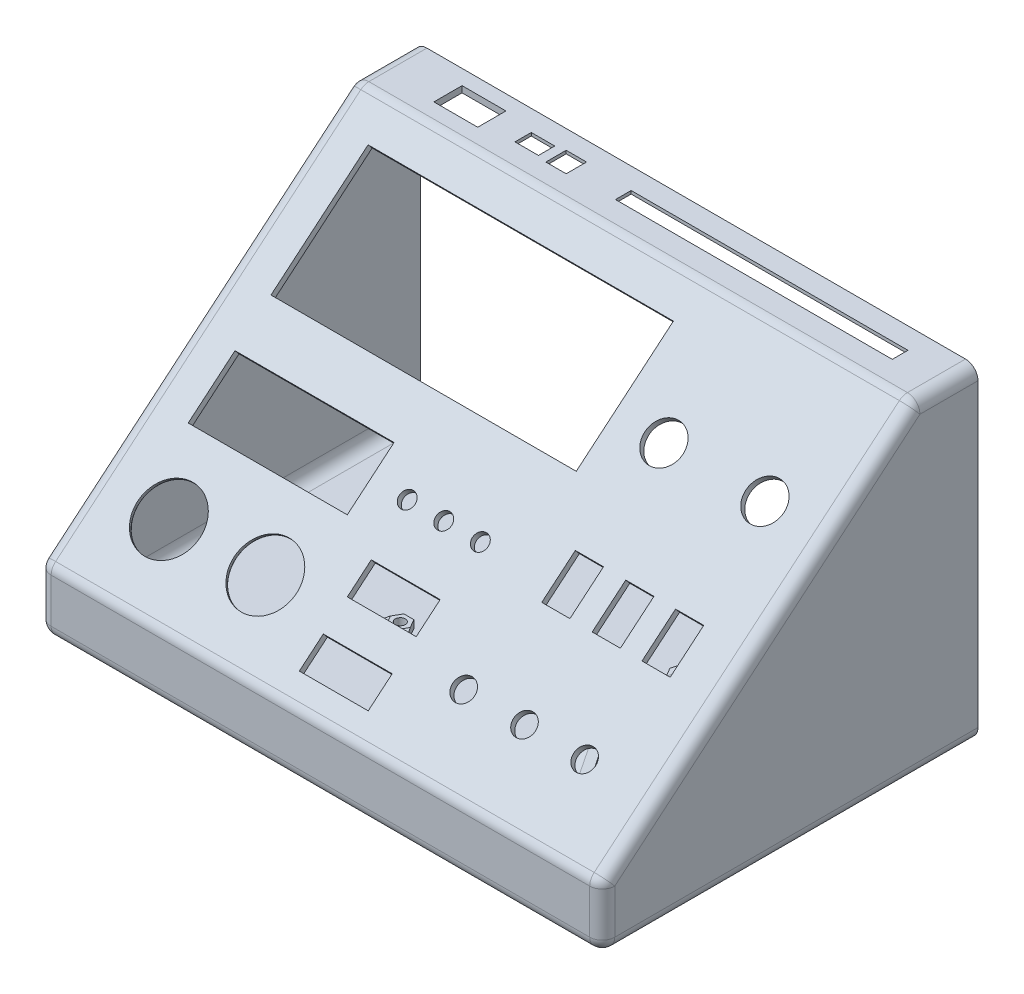
SolidWorks part; units mm, degrees
ref_plane "Front Plane" through (0, 0, 0) normal (0, 0, 1) x (1, 0, 0)
ref_plane "Top Plane" through (0, 0, 0) normal (0, 1, 0) x (1, 0, 0)
ref_plane "Right Plane" through (0, 0, 0) normal (1, 0, 0) x (0, 0, -1)
sketch "Sketch1" plane through (0, 0, 0) normal (0, 1, 0) x (1, 0, 0)
  line L1 (-90, -60) -> (90, -60)
  line L2 (-90, -60) -> (-90, 60)
  line L3 (-90, 60) -> (90, 60)
  line L4 (90, -60) -> (90, 60)
  line L5 (-90, -60) -> (90, 60) construction
  line L6 (-90, 60) -> (90, -60) construction
  point P0 (0, 0)
  dimension "D1" = 180
  dimension "D2" = 120
extrude "Boss-Extrude1" add sketch "Sketch1" along normal blind 20
sketch "Sketch2" plane through (-90, 0, 0) normal (-1, 0, 0) x (0, 0, 1)
  line L0 (60, 20) -> (-40, 103.91)
  line L1 (-60, 20) -> (60, 20) construction
  line L2 (60, 20) -> (60, 0) construction
  line L3 (-60, 20) -> (-60, 103.91)
  line L4 (-60, 103.91) -> (-40, 103.91)
  line L5 (-60, 20) -> (60, 20)
  dimension "D1" = 40
  dimension "D2" = 100
extrude "Boss-Extrude2" add sketch "Sketch2" against normal up to surface (180 mm away) up to face at (90, 10, 0)
shell "Shell3" thickness 2 removed face at (0, 51.955, -60)
fillet "Fillet1" radius 4 11 edges at (-90, 10, 60) (90, 10, 60) (0, 0, 60) (0, 20, 60) (-90, 61.955, 10) (0, 103.91, -40) (90, 61.955, 10) (-90, 103.91, -50) (-90, 0, 0) (90, 0, 0) (90, 103.91, -50)
fillet "Fillet2" radius 4 11 edges at (88, 10.5337, 58) (0, 19.0674, 58) (-88, 10.5337, 58) (0, 2, 58) (88, 101.91, -50.364) (0, 101.91, -40.7279) (-88, 101.91, -50.364) (88, 60.4887, 8.636) (88, 2, -1) (-88, 60.4887, 8.636) (-88, 2, -1)
sketch "Sketch4" plane through (0, 2, 0) normal (0, 1, 0) x (1, 0, 0)
  line L0 (-84, -54) -> (84, -54) construction
  line L1 (0, -54) -> (0, 60) construction
  line L2 (84, 60) -> (-84, 60) construction
  line L3 (0, 0) -> (0, 60) construction
  line L4 (0, 3) -> (0, 60) construction
  line L5 (0, 60) -> (0, 31.5) construction
  line L6 (0, 31.5) -> (0, 3) construction
  line L7 (0, 3) -> (0, 60.9981) construction
  line L8 (0, 60.9981) -> (0, 31.9991) construction
  line L9 (0, 31.9991) -> (0, 3) construction
  line L10 (0, -7.5005) -> (0, 42.4995)
  line L11 (35, 42.4995) -> (-35, 42.4995)
  line L12 (35, 42.4995) -> (35, -7.5005)
  line L13 (35, -7.5005) -> (-35, -7.5005)
  line L14 (-35, 42.4995) -> (-35, -7.5005)
  line L15 (35, 42.4995) -> (-35, -7.5005) construction
  line L16 (35, -7.5005) -> (-35, 42.4995) construction
  line L17 (35, -7.5005) -> (31, -7.5005)
  line L18 (31, -7.5005) -> (31, -3.5005)
  line L19 (34.1754, -3.5005) -> (32.5877, -0.7505)
  line L20 (32.5877, -0.7505) -> (29.4123, -0.7505)
  line L21 (29.4123, -0.7505) -> (27.8246, -3.5005)
  line L22 (27.8246, -3.5005) -> (29.4123, -6.2505)
  line L23 (29.4123, -6.2505) -> (32.5877, -6.2505)
  line L24 (32.5877, -6.2505) -> (34.1754, -3.5005)
  line L25 (-35, 17.4995) -> (35, 17.4995)
  line L26 (32.5877, 41.2495) -> (34.1754, 38.4995)
  line L27 (29.4123, 41.2495) -> (32.5877, 41.2495)
  line L28 (27.8246, 38.4995) -> (29.4123, 41.2495)
  line L29 (29.4123, 35.7495) -> (27.8246, 38.4995)
  line L30 (32.5877, 35.7495) -> (29.4123, 35.7495)
  line L31 (34.1754, 38.4995) -> (32.5877, 35.7495)
  line L32 (-29.4123, 41.2495) -> (-32.5877, 41.2495)
  line L33 (-27.8246, 38.4995) -> (-29.4123, 41.2495)
  line L34 (-29.4123, 35.7495) -> (-27.8246, 38.4995)
  line L35 (-32.5877, 35.7495) -> (-29.4123, 35.7495)
  line L36 (-34.1754, 38.4995) -> (-32.5877, 35.7495)
  line L37 (-32.5877, 41.2495) -> (-34.1754, 38.4995)
  line L38 (-32.5877, -6.2505) -> (-34.1754, -3.5005)
  line L39 (-29.4123, -6.2505) -> (-32.5877, -6.2505)
  line L40 (-27.8246, -3.5005) -> (-29.4123, -6.2505)
  line L41 (-29.4123, -0.7505) -> (-27.8246, -3.5005)
  line L42 (-32.5877, -0.7505) -> (-29.4123, -0.7505)
  line L43 (-34.1754, -3.5005) -> (-32.5877, -0.7505)
  circle A0 centre (31, -3.5005) radius 2.75 construction
  point P11 (0, 17.4995)
  dimension "D1" = 70
  dimension "D2" = 50
  dimension "D3" = 4
  dimension "D4" = 4
  dimension "D5" = 5.5
extrude "Boss-Extrude3" add sketch "Sketch4" along normal blind 2.5 contours L23 L24 L19 L20 L21 L22 | L31 L26 L27 L28 L29 L30 | L32 L37 L36 L35 L34 L33 | L43 L38 L39 L40 L41 L42 region at (30.2061, 2, 6.1665) region at (31, 2, -38.4995) region at (-31, 2, -38.4995) region at (-31, 2, 3.5005)
sketch "Sketch14" plane through (0, 4.5, 0) normal (0, 1, 0) x (1, 0, 0)
  line L0 (34.1754, -3.5005) -> (27.8246, -3.5005) construction
  line L1 (29.4123, -0.7505) -> (27.8246, -3.5005) construction
  line L2 (27.8246, -3.5005) -> (29.4123, -6.2505) construction
  line L3 (27.8246, -3.5005) -> (-27.8246, -3.5005) construction
  line L4 (-27.8246, -3.5005) -> (0, -3.5005) construction
  line L5 (27.8246, 38.4995) -> (-27.8246, 38.4995) construction
  line L6 (-27.8246, 38.4995) -> (0, 38.4995) construction
  line L7 (0, 38.4995) -> (0, -3.5005) construction
  line L8 (0, 17.4995) -> (25.4605, 17.4995)
  circle A0 centre (31, -3.5005) radius 1.6
  circle A1 centre (31, 38.4995) radius 1.6
  circle A2 centre (-31, 38.4995) radius 1.6
  circle A3 centre (-31, -3.5005) radius 1.6
extrude "Cut-Extrude10" cut sketch "Sketch14" against normal blind 3.2 contours A1 | A3 | A2 | A0 region at (31, 4.5, -38.4995)
sketch "Sketch7" plane through (0, 103.91, 0) normal (0, 1, 0) x (1, 0, 0)
  line L0 (-86, 60) -> (-86, 41.4559) construction
  line L1 (-86, 41.4559) -> (-86, 50.7279) construction
  line L2 (-86, 50.7279) -> (-56, 50.7279) construction
  line L3 (-56, 46.2279) -> (-56, 55.2279)
  line L4 (-56, 55.2279) -> (-70, 55.2279)
  line L5 (-70, 55.2279) -> (-70, 46.2279)
  line L6 (-70, 46.2279) -> (-56, 46.2279)
  point P9 (-56, 50.7279)
  dimension "D1" = 9
  dimension "D2" = 14
  dimension "D3" = 30
extrude "Cut-Extrude3" cut sketch "Sketch7" against normal up to next
sketch "Sketch8" plane through (0, 41.2807, 34.6386) normal (0, 0.766, 0.6428) x (1, 0, 0)
  line L0 (-86, 95.9779) -> (86, 95.9779) construction
  line L1 (86, 95.9779) -> (86, -31.2417) construction
  line L2 (86, -31.2417) -> (-86, -31.2417) construction
  line L3 (-86, -31.2417) -> (-86, 95.9779) construction
  line L4 (-76, 95.9779) -> (-76, -31.2417)
  line L5 (-86, 85.9779) -> (86, 85.9779)
  line L6 (86, -31.2417) -> (86, 95.9779) construction
  line L7 (-86, -31.2417) -> (86, -31.2417) construction
  line L8 (76, -31.2417) -> (76, 95.9779)
  line L9 (86, -21.2417) -> (-86, -21.2417)
  line L10 (-86, 95.9779) -> (-86, -31.2417) construction
  line L11 (86, 95.9779) -> (-86, 95.9779) construction
  line L12 (-73.5, 95.9779) -> (-73.5, 93.4779)
  line L13 (-76, 85.9779) -> (21.5, 85.9779)
  line L14 (-76, 85.9779) -> (-76, 45.4779)
  line L15 (-76, 45.4779) -> (21.5, 45.4779)
  line L16 (21.5, 85.9779) -> (21.5, 45.4779)
  line L17 (-76, 85.9779) -> (21.5, 85.9779) construction
  line L18 (-27.25, 85.9779) -> (-27.25, 45.4779) construction
  line L19 (-45.177, 65.7279) -> (-9.323, 65.7279)
  circle A0 centre (-73.5, 93.4779) radius 1.35
  circle A1 centre (-73.5, 37.9779) radius 1.35
  circle A2 centre (19, 37.9779) radius 1.35
  circle A3 centre (19, 93.4779) radius 1.35
  point P36 (-27.25, 65.7279)
  dimension "D1" = 10
  dimension "D2" = 10
  dimension "D3" = 10
  dimension "D4" = 10
  dimension "D5" = 97.5
  dimension "D6" = 40.5
  dimension "D7" = 2.5
  dimension "D8" = 2.5
extrude "Boss-Extrude4" add sketch "Sketch8" against normal blind 5 contours A0 | A3 | A2 | A1
extrude "Cut-Extrude4" cut sketch "Sketch8<3>" against normal blind 5 contours L16 L5 L4 L15 region at (-27.25, 95.8676, -30.4155)
sketch "Sketch8<3>" plane through (0, 41.2807, 34.6386) normal (0, 0.766, 0.6428) x (1, 0, 0) same geometry as "Sketch8"
sketch "Sketch9" plane through (0, 41.2807, 34.6386) normal (0, 0.766, 0.6428) x (1, 0, 0)
  line L0 (-76, 85.9779) -> (-76, 30.4779)
  line L1 (-76, 45.4779) -> (21.5, 45.4779) construction
  line L3 (-76, 30.4779) -> (-25.2, 30.4779)
  line L4 (-76, 30.4779) -> (-76, 10.9779)
  line L5 (-76, 10.9779) -> (-25.2, 10.9779)
  line L6 (-25.2, 30.4779) -> (-25.2, 10.9779)
  dimension "D1" = 15
  dimension "D2" = 50.8
  dimension "D3" = 19.5
extrude "Cut-Extrude5" cut sketch "Sketch9" against normal blind 5 contours L6 L3 L4 L5 region at (-50.6, 54.6044, 18.7601)
sketch "Sketch10" plane through (0, 41.2807, 34.6386) normal (0, 0.766, 0.6428) x (1, 0, 0)
  line L0 (-25.2, 30.4779) -> (-25.2, 10.9779) construction
  line L1 (21.5, 45.4779) -> (21.5, 10.9779)
  line L2 (-25.2, 30.4779) -> (21.5, 30.4779) construction
  line L3 (21.5, 30.4779) -> (21.5, 10.9779) construction
  line L4 (21.5, 10.9779) -> (-25.2, 10.9779) construction
  line L5 (-1.85, 10.9779) -> (-1.85, 30.4779) construction
  line L6 (-1.85, 30.4779) -> (-1.85, 10.9779) construction
  line L7 (-1.85, 20.7279) -> (21.5, 20.7279) construction
  line L8 (-1.85, 20.7279) -> (-25.2, 20.7279) construction
  circle A0 centre (-1.85, 20.7279) radius 2.525
  circle A1 centre (-13.525, 20.7279) radius 2.525
  circle A2 centre (9.825, 20.7279) radius 2.525
extrude "Cut-Extrude6" cut sketch "Sketch10" against normal blind 5 contours A1 | A0 | A2 region at (-1.85, 54.6044, 18.7601) region at (-13.525, 54.6044, 18.7601) region at (9.825, 54.6044, 18.7601)
sketch "Sketch11" plane through (0, 41.2807, 34.6386) normal (0, 0.766, 0.6428) x (1, 0, 0)
  line L0 (21.5, 85.9779) -> (21.5, 45.4779) construction
  line L1 (86, 95.9779) -> (-86, 95.9779) construction
  line L2 (21.5, 65.7279) -> (86, 65.7279) construction
  line L3 (86, -31.2417) -> (86, 95.9779) construction
  line L4 (86, 65.7279) -> (53.75, 65.7279) construction
  line L5 (53.75, 65.7279) -> (21.5, 65.7279) construction
  line L6 (69.875, 67.1029) -> (69.875, 54.8529)
  line L7 (86, 65.7279) -> (53.75, 65.7279) construction
  line L8 (53.75, 65.7279) -> (86, 65.7279) construction
  line L9 (86, 65.7279) -> (69.875, 65.7279) construction
  line L10 (69.875, 65.7279) -> (69.875, 60.9779) construction
  line L11 (53.75, 65.7279) -> (53.75, 56.7637)
  circle A0 centre (69.875, 60.9779) radius 6.125
  circle A1 centre (37.625, 60.9779) radius 6.125
  dimension "D1" = 12.25
  dimension "D2" = 35
extrude "Cut-Extrude7" cut sketch "Sketch11" against normal blind 5 contours A1 | L6 A0 | L6 A0 region at (72.4745, 80.4766, -12.0732) region at (67.2755, 80.4766, -12.0732) region at (37.625, 80.4766, -12.0732)
sketch "Sketch12" plane through (0, 41.2807, 34.6386) normal (0, 0.766, 0.6428) x (1, 0, 0)
  line L0 (-76, 10.9779) -> (-76, -4.0221)
  line L1 (-76, -31.2417) -> (-76, -16.2417)
  line L2 (-86, -31.2417) -> (86, -31.2417) construction
  line L3 (-76, -4.0221) -> (-76, -16.2417) construction
  line L4 (-25.2, 10.9779) -> (-25.2, -31.2417)
  line L5 (-25.2, 30.4779) -> (-25.2, 10.9779) construction
  line L6 (-25.2, -31.2417) -> (-25.2, -10.1319)
  line L7 (-25.2, -10.1319) -> (-76, -10.1319)
  line L8 (-50.6, -10.1319) -> (-76, -10.1319) construction
  line L9 (-76, -10.1319) -> (-63.3, -10.1319) construction
  line L10 (-63.3, -10.1319) -> (-63.3, -2.7605) construction
  line L11 (-63.3, -2.7605) -> (-63.3, -10.1319) construction
  line L12 (-63.3, -10.1319) -> (-50.6, -10.1319) construction
  line L13 (-50.6, -10.1319) -> (-25.2, -10.1319) construction
  line L14 (-37.9, -10.1319) -> (-37.9, -2.7605) construction
  circle A2 centre (-66, -10.1319) radius 10
  circle A3 centre (-35.2, -10.1319) radius 10
  dimension "D1" = 15
  dimension "D2" = 15
extrude "Cut-Extrude8" cut sketch "Sketch12" against normal blind 5 contours L7 A2 | L7 A3 | L7 A3 | L7 A2 region at (-66, 32.04, 45.6513) region at (-35.2, 37.4961, 39.1489) region at (-35.2, 32.04, 45.6513) region at (-66, 37.4961, 39.1489)
fillet "Fillet4" radius 1.5 2 edges at (-35.2, 26.8081, 48.775) (-66, 26.8081, 48.775)
sketch "Sketch13" plane through (0, 41.2807, 34.6386) normal (0, 0.766, 0.6428) x (1, 0, 0)
  line L0 (-25.2, -10.1319) -> (32.7814, -10.1319)
  line L1 (21.5, 45.4779) -> (21.5, -10.1319)
  line L2 (21.5, -10.1319) -> (-25.2, -10.1319) construction
  line L3 (-25.2, -10.1319) -> (21.5, -10.1319) construction
  line L4 (21.5, -10.1319) -> (-1.85, -10.1319) construction
  line L5 (-25.2, 10.9779) -> (21.5, 10.9779)
  line L6 (-1.85, -10.1319) -> (-1.85, 10.9779) construction
  line L7 (-12.85, -25.1319) -> (9.15, -25.1319)
  line L8 (-12.85, -5.1319) -> (9.15, -5.1319)
  line L9 (-12.85, -5.1319) -> (-12.85, 4.8681)
  line L10 (-12.85, 4.8681) -> (9.15, 4.8681)
  line L11 (9.15, -5.1319) -> (9.15, 4.8681)
  line L12 (-12.85, -5.1319) -> (9.15, 4.8681) construction
  line L13 (-12.85, 4.8681) -> (9.15, -5.1319) construction
  line L14 (9.15, -15.1319) -> (9.15, -25.1319)
  line L15 (-12.85, -15.1319) -> (9.15, -15.1319)
  line L16 (-12.85, -15.1319) -> (-12.85, -25.1319)
  circle A0 centre (-35.2, -10.1319) radius 10 construction
  point P11 (-1.85, 0.423)
  dimension "D1" = 22
  dimension "D2" = 10
  dimension "D3" = 5
extrude "Cut-Extrude9" cut sketch "Sketch13" against normal blind 5 contours L8 L11 L10 L9 | L15 L16 L7 L14 region at (-1.85, 28.3402, 50.0605) region at (-1.85, 41.1959, 34.7397)
chamfer "Chamfer1" distance 2.5 angle 75 12 edges at (-28.6184, 2, 4.8755) (-31, 2, 6.2505) (-33.3816, 2, 4.8755) (-33.3816, 2, -37.1245) (-31, 2, -35.7495) (-28.6184, 2, -37.1245) (28.6184, 2, -37.1245) (31, 2, -35.7495) (33.3816, 2, -37.1245) (33.3816, 2, 4.8755) (28.6184, 2, 4.8755) (31, 2, 6.2505) first distance on face at (-28.6184, 3.25, 4.8755) first distance on face at (-31, 3.25, 6.2505) first distance on face at (-33.3816, 3.25, 4.8755) first distance on face at (-33.3816, 3.25, -37.1245) first distance on face at (-31, 3.25, -35.7495) first distance on face at (-28.6184, 3.25, -37.1245) first distance on face at (28.6184, 3.25, -37.1245) first distance on face at (31, 3.25, -35.7495) first distance on face at (33.3816, 3.25, -37.1245) first distance on face at (33.3816, 3.25, 4.8755) first distance on face at (28.6184, 3.25, 4.8755) first distance on face at (31, 3.25, 6.2505)
sketch "Sketch15" plane through (0, 41.2807, 34.6386) normal (0, 0.766, 0.6428) x (1, 0, 0)
  line L0 (21.5, 45.4779) -> (21.9808, 0)
  line L1 (21.5, 45.4779) -> (86, 45.4779) construction
  line L2 (86, -31.2417) -> (86, 95.9779) construction
  line L3 (86, 45.4779) -> (86, 0) construction
  line L4 (86, 0) -> (21.9808, 0) construction
  line L5 (86, 22.739) -> (21.7404, 22.739) construction
  line L6 (53.8702, 22.739) -> (86, 22.739) construction
  line L7 (49.3702, 15.739) -> (58.3702, 15.739)
  line L8 (49.3702, 15.739) -> (49.3702, 29.739)
  line L9 (49.3702, 29.739) -> (58.3702, 29.739)
  line L10 (58.3702, 15.739) -> (58.3702, 29.739)
  line L11 (49.3702, 15.739) -> (58.3702, 29.739) construction
  line L12 (49.3702, 29.739) -> (58.3702, 15.739) construction
  line L13 (86, 22.739) -> (69.9351, 22.739) construction
  line L14 (69.9351, 22.739) -> (69.9351, 40.2733) construction
  line L15 (69.9351, 40.2733) -> (69.9351, 22.739) construction
  line L16 (69.9351, 22.739) -> (53.8702, 22.739) construction
  line L17 (53.8702, 22.739) -> (21.7404, 22.739) construction
  line L18 (21.7404, 22.739) -> (37.8053, 22.739) construction
  line L19 (37.8053, 22.739) -> (37.8053, 31.5062) construction
  line L20 (33.1892, 15.833) -> (42.1892, 15.833)
  line L21 (33.1892, 15.833) -> (33.1892, 29.833)
  line L22 (33.1892, 29.833) -> (42.1892, 29.833)
  line L23 (42.1892, 15.833) -> (42.1892, 29.833)
  line L24 (65.3123, 15.6839) -> (74.3123, 15.6839)
  line L25 (65.3123, 15.6839) -> (65.3123, 29.6839)
  line L26 (65.3123, 29.6839) -> (74.3123, 29.6839)
  line L27 (74.3123, 15.6839) -> (74.3123, 29.6839)
  point P9 (53.8702, 22.739)
  dimension "D1" = 9
  dimension "D2" = 14
extrude "Cut-Extrude11" cut sketch "Sketch15" against normal blind 3.2 contours L24 L27 L26 L25 | L7 L10 L9 L8 | L20 L23 L22 L21 region at (53.8702, 55.897, 17.2196) region at (37.6892, 55.9575, 17.1476) region at (69.8123, 55.8616, 17.2618)
sketch "Sketch16" plane through (0, 41.2807, 34.6386) normal (0, 0.766, 0.6428) x (1, 0, 0)
  line L0 (9.15, 4.8681) -> (9.15, -25.1319) construction
  line L1 (9.15, -25.1319) -> (9.15, -10.1319) construction
  line L2 (9.15, -10.1319) -> (86, -10.1319) construction
  line L3 (86, -31.2417) -> (86, 95.9779) construction
  line L4 (47.575, -10.1319) -> (86, -10.1319) construction
  line L5 (86, -10.1319) -> (47.575, -10.1319) construction
  line L6 (47.575, -10.1319) -> (9.15, -10.1319) construction
  line L7 (47.575, -10.1319) -> (86, -10.1319) construction
  circle A0 centre (66.7875, -10.1319) radius 3.5
  circle A1 centre (47.575, -10.1319) radius 3.5
  circle A2 centre (28.1503, -10.1319) radius 3.5
extrude "Cut-Extrude12" cut sketch "Sketch16" against normal blind 3.2 contours A0 | A2 | A1 region at (66.7875, 34.7681, 42.4001)
sketch "Sketch17" plane through (0, 0, 0) normal (0, -1, 0) x (1, 0, 0)
  line L0 (-86, 56) -> (-78.2218, 48.2218)
  line L1 (0, 0) -> (25.5086, 0)
  line L2 (57.1505, 0) -> (-57.1505, 0) construction
  line L3 (25.5086, 0) -> (0, 0)
  line L4 (0, 0) -> (0, 11.6481)
  line L5 (0, 0) -> (0, -3.057)
  line L6 (0, -3.057) -> (9.4489, -3.057)
  line L7 (0, -1.5285) -> (4.9263, -1.5285)
  circle A0 centre (-78.2218, 48.2218) radius 6
  circle A1 centre (-78.2218, 48.2218) radius 7
  circle A2 centre (78.2218, 48.2218) radius 7
  circle A3 centre (78.2218, 48.2218) radius 6
  circle A4 centre (78.2218, -51.2788) radius 7
  circle A5 centre (78.2218, -51.2788) radius 6
  circle A6 centre (-78.2218, -51.2788) radius 7
  circle A7 centre (-78.2218, -51.2788) radius 6
  dimension "D1" = 11
extrude "Boss-Extrude5" add sketch "Sketch17" along normal blind 0.5 contours A4 A5 | A2 A3 | A1 A0 | A6 A7 region at (-75.6188, 0, 54.5061) region at (71.4198, 0, 48.2218) region at (71.4198, 0, -51.2788) region at (-85.0238, 0, -51.2788)
fillet "Fillet7" radius 0.5 8 edges at (78.2218, -0.5, -58.2788) (78.2218, -0.5, -57.2788) (-78.2218, -0.5, -57.2788) (-78.2218, -0.5, -58.2788) (-78.2218, -0.5, 41.2218) (-78.2218, -0.5, 42.2218) (78.2218, -0.5, 42.2218) (78.2218, -0.5, 41.2218)
sketch "Sketch18" plane through (0, 101.91, 0) normal (0, -1, 0) x (1, 0, 0)
  line L0 (-56, -50.7279) -> (-51, -50.7279)
  line L1 (-56, -55.2279) -> (-56, -46.2279) construction
  line L2 (-51, -50.7279) -> (-51, -44.1838)
  line L3 (-51, -44.1838) -> (-51, -50.7279)
  line L4 (-51, -50.7279) -> (-51, -58)
  line L5 (84, -60) -> (-84, -60) construction
  line L6 (-51, -58) -> (79, -58)
  line L7 (-51, -58) -> (-51, -44.1838)
  line L8 (-51, -44.1838) -> (79, -44.1838)
  line L9 (79, -58) -> (79, -44.1838)
  line L10 (84, -42.1838) -> (-84, -42.1838) construction
  line L11 (84, -60) -> (84, -42.1838) construction
  dimension "D1" = 5
  dimension "D2" = 2
  dimension "D3" = 2
  dimension "D4" = 5
extrude "Cut-Extrude13" cut sketch "Sketch18" against normal blind 1 contours L6 L9 L8 L2 L4 region at (14, 101.91, -51.0919)
fillet "Fillet8" radius 1 4 edges at (-51, 102.91, -51.0919) (14, 102.91, -44.1838) (79, 102.91, -51.0919) (14, 102.91, -58)
sketch "Sketch19" plane through (0, 103.91, 0) normal (0, 1, 0) x (1, 0, 0)
  line L0 (-56, 50.7279) -> (-46, 50.7279)
  line L1 (-56, 46.2279) -> (-56, 55.2279) construction
  line L2 (-46, 50.7279) -> (-42.25, 50.7279)
  line L3 (-42.25, 50.7279) -> (-32.25, 50.7279)
  line L4 (-38.5, 53.3279) -> (-46, 53.3279)
  line L5 (-38.5, 53.3279) -> (-38.5, 48.1279)
  line L6 (-38.5, 48.1279) -> (-46, 48.1279)
  line L7 (-46, 53.3279) -> (-46, 48.1279)
  line L8 (-38.5, 53.3279) -> (-46, 48.1279) construction
  line L9 (-38.5, 48.1279) -> (-46, 53.3279) construction
  line L10 (-29, 50.7279) -> (-14, 50.7279)
  line L11 (-35.5, 47.4779) -> (-29, 47.4779)
  line L12 (-35.5, 47.4779) -> (-35.5, 53.9779)
  line L13 (-35.5, 53.9779) -> (-29, 53.9779)
  line L14 (-29, 47.4779) -> (-29, 53.9779)
  line L15 (-35.5, 47.4779) -> (-29, 53.9779) construction
  line L16 (-35.5, 53.9779) -> (-29, 47.4779) construction
  line L17 (-14, 50.7279) -> (-14, 53.2279)
  line L18 (-14, 53.2279) -> (74.4, 53.2279)
  line L19 (74.4, 53.2279) -> (74.4, 48.2279)
  line L20 (74.4, 48.2279) -> (-14, 48.2279)
  line L21 (-14, 48.2279) -> (-14, 50.7279)
  dimension "D1" = 10
  dimension "D2" = 3.75
  dimension "D3" = 5.2
  dimension "D4" = 10
  dimension "D5" = 6.5
  dimension "D6" = 6.5
  dimension "D7" = 15
  dimension "D8" = 5
  dimension "D9" = 2.5
  dimension "D10" = 88.4
extrude "Cut-Extrude14" cut sketch "Sketch19" against normal blind 1.2 contours L21 L20 L19 L18 L17 | L11 L14 L13 L12 | L2 L7 L6 L5 L3 | L4 L7 L2 L3 L5 region at (-42.25, 103.91, -52.0279) region at (30.2, 103.91, -50.7279) region at (-35.4081, 103.91, -52.3529) region at (-42.25, 103.91, -49.4279)
sketch "Sketch20" plane through (-90, 0, 0) normal (-1, 0, 0) x (0, 0, 1)
  line L0 (-60, 99.91) -> (-45, 99.91)
  line L1 (-41.4559, 99.91) -> (-60, 99.91) construction
  line L2 (-45, 99.91) -> (-45, 84.91)
  line L3 (-45, 84.91) -> (-60, 84.91)
  line L4 (-60, 99.91) -> (-60, 4) construction
  line L5 (-60, 84.91) -> (-60, 99.91)
  line L6 (-60, 99.91) -> (-41.4559, 99.91) construction
  line L7 (-52.5, 99.91) -> (-52.5, 84.91)
  circle A0 centre (-52.5, 92.41) radius 6
  dimension "D1" = 15
  dimension "D2" = 15
extrude "Cut-Extrude15" cut sketch "Sketch20" against normal blind 10 contours L7 A0 | L7 A0 region at (-90, 92.41, -49.9535) region at (-90, 92.41, -55.0465)
sketch "Sketch21" plane through (0, 0, -60) normal (0, 0, -1) x (-1, 0, 0)
  line L0 (-83, 101.91) -> (-84, 101.91)
  line L1 (-84, 101.91) -> (84, 101.91) construction
  line L2 (-88, 97.91) -> (-88, 96.91)
  line L3 (-88, 97.91) -> (-88, 6) construction
  line L4 (-88, 96.91) -> (-88, 97.91)
  line L5 (-83, 101.91) -> (-83, 96.91)
  line L6 (-83, 96.91) -> (-88, 96.91)
  arc A0 (-88, 97.91) -> (-84, 101.91) centre (-84, 97.91) cw
  line M13 (-88, 6) -> (-88, 97.91)
  arc M14 (-88, 97.91) -> (-84, 101.91) centre (-84, 97.91) cw
  line M15 (-84, 101.91) -> (84, 101.91)
  dimension "D1" = 1
  dimension "D2" = 1
extrude "Boss-Extrude6" add sketch "Sketch21" against normal up to next contours L6 L5 M15 M14 M13 region at (85.2442, 99.1542, -60)
sketch "Sketch22" plane through (0, 0, -60) normal (0, 0, -1) x (-1, 0, 0)
  line L0 (-83, 96.91) -> (-85.5456, 99.4555)
  circle A0 centre (-85.5456, 99.4555) radius 1.6
  dimension "D1" = 3.6
extrude "Cut-Extrude16" cut sketch "Sketch22" against normal blind 16 contours A0 region at (84.1092, 98.8606, -60)
fillet "Fillet9" radius 1 1 edges at (83, 96.91, -47.3846)
